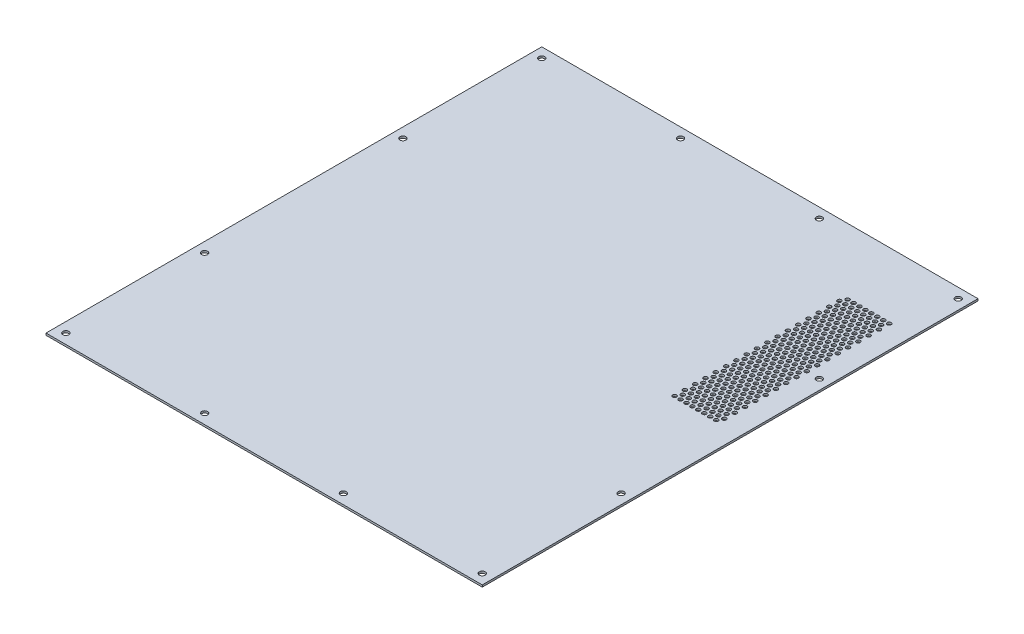
SolidWorks part; units mm, degrees
ref_plane "Front Plane" through (0, 0, 0) normal (0, 0, 1) x (1, 0, 0)
ref_plane "Top Plane" through (0, 0, 0) normal (0, 1, 0) x (1, 0, 0)
ref_plane "Right Plane" through (0, 0, 0) normal (1, 0, 0) x (0, 0, -1)
sketch "Sketch1" plane through (0, 0, 0) normal (0, 1, 0) x (1, 0, 0)
  line L0 (20, 20) -> (20, 480) construction
  line L1 (0, 0) -> (440, 0)
  line L2 (0, 0) -> (0, 500)
  line L3 (0, 500) -> (440, 500)
  line L4 (440, 0) -> (440, 500)
  line L5 (20, 480) -> (420, 480) construction
  line L6 (420, 20) -> (420, 480) construction
  line L7 (20, 20) -> (420, 20) construction
  line L9 (420, 440) -> (370, 440) construction
  line L10 (420, 440) -> (420, 260) construction
  line L11 (420, 260) -> (370, 260) construction
  line L12 (370, 440) -> (370, 260) construction
  circle A0 centre (372, 262) radius 2
  circle A1 centre (375, 267.1962) radius 2
  circle A2 centre (381, 267.1962) radius 2
  circle A3 centre (378, 262) radius 2
  circle A4 centre (387, 267.1962) radius 2
  circle A5 centre (384, 262) radius 2
  circle A6 centre (393, 267.1962) radius 2
  circle A7 centre (390, 262) radius 2
  circle A8 centre (399, 267.1962) radius 2
  circle A9 centre (396, 262) radius 2
  circle A10 centre (405, 267.1962) radius 2
  circle A11 centre (402, 262) radius 2
  circle A12 centre (411, 267.1962) radius 2
  circle A13 centre (408, 262) radius 2
  circle A14 centre (417, 267.1962) radius 2
  circle A15 centre (414, 262) radius 2
  circle A16 centre (381, 277.5862) radius 2
  circle A17 centre (378, 272.39) radius 2
  circle A18 centre (387, 277.5862) radius 2
  circle A19 centre (384, 272.39) radius 2
  circle A20 centre (393, 277.5862) radius 2
  circle A21 centre (390, 272.39) radius 2
  circle A22 centre (399, 277.5862) radius 2
  circle A23 centre (396, 272.39) radius 2
  circle A24 centre (405, 277.5862) radius 2
  circle A25 centre (402, 272.39) radius 2
  circle A26 centre (411, 277.5862) radius 2
  circle A27 centre (408, 272.39) radius 2
  circle A28 centre (417, 277.5862) radius 2
  circle A29 centre (414, 272.39) radius 2
  circle A30 centre (381, 287.9762) radius 2
  circle A31 centre (378, 282.78) radius 2
  circle A32 centre (387, 287.9762) radius 2
  circle A33 centre (384, 282.78) radius 2
  circle A34 centre (393, 287.9762) radius 2
  circle A35 centre (390, 282.78) radius 2
  circle A36 centre (399, 287.9762) radius 2
  circle A37 centre (396, 282.78) radius 2
  circle A38 centre (405, 287.9762) radius 2
  circle A39 centre (402, 282.78) radius 2
  circle A40 centre (411, 287.9762) radius 2
  circle A41 centre (408, 282.78) radius 2
  circle A42 centre (417, 287.9762) radius 2
  circle A43 centre (414, 282.78) radius 2
  circle A44 centre (381, 298.3662) radius 2
  circle A45 centre (378, 293.17) radius 2
  circle A46 centre (387, 298.3662) radius 2
  circle A47 centre (384, 293.17) radius 2
  circle A48 centre (393, 298.3662) radius 2
  circle A49 centre (390, 293.17) radius 2
  circle A50 centre (399, 298.3662) radius 2
  circle A51 centre (396, 293.17) radius 2
  circle A52 centre (405, 298.3662) radius 2
  circle A53 centre (402, 293.17) radius 2
  circle A54 centre (411, 298.3662) radius 2
  circle A55 centre (408, 293.17) radius 2
  circle A56 centre (417, 298.3662) radius 2
  circle A57 centre (414, 293.17) radius 2
  circle A58 centre (381, 308.7562) radius 2
  circle A59 centre (378, 303.56) radius 2
  circle A60 centre (387, 308.7562) radius 2
  circle A61 centre (384, 303.56) radius 2
  circle A62 centre (393, 308.7562) radius 2
  circle A63 centre (390, 303.56) radius 2
  circle A64 centre (399, 308.7562) radius 2
  circle A65 centre (396, 303.56) radius 2
  circle A66 centre (405, 308.7562) radius 2
  circle A67 centre (402, 303.56) radius 2
  circle A68 centre (411, 308.7562) radius 2
  circle A69 centre (408, 303.56) radius 2
  circle A70 centre (417, 308.7562) radius 2
  circle A71 centre (414, 303.56) radius 2
  circle A72 centre (381, 319.1462) radius 2
  circle A73 centre (378, 313.95) radius 2
  circle A74 centre (387, 319.1462) radius 2
  circle A75 centre (384, 313.95) radius 2
  circle A76 centre (393, 319.1462) radius 2
  circle A77 centre (390, 313.95) radius 2
  circle A78 centre (399, 319.1462) radius 2
  circle A79 centre (396, 313.95) radius 2
  circle A80 centre (405, 319.1462) radius 2
  circle A81 centre (402, 313.95) radius 2
  circle A82 centre (411, 319.1462) radius 2
  circle A83 centre (408, 313.95) radius 2
  circle A84 centre (417, 319.1462) radius 2
  circle A85 centre (414, 313.95) radius 2
  circle A86 centre (381, 329.5362) radius 2
  circle A87 centre (378, 324.34) radius 2
  circle A88 centre (387, 329.5362) radius 2
  circle A89 centre (384, 324.34) radius 2
  circle A90 centre (393, 329.5362) radius 2
  circle A91 centre (390, 324.34) radius 2
  circle A92 centre (399, 329.5362) radius 2
  circle A93 centre (396, 324.34) radius 2
  circle A94 centre (405, 329.5362) radius 2
  circle A95 centre (402, 324.34) radius 2
  circle A96 centre (411, 329.5362) radius 2
  circle A97 centre (408, 324.34) radius 2
  circle A98 centre (417, 329.5362) radius 2
  circle A99 centre (414, 324.34) radius 2
  circle A100 centre (381, 339.9262) radius 2
  circle A101 centre (378, 334.73) radius 2
  circle A102 centre (387, 339.9262) radius 2
  circle A103 centre (384, 334.73) radius 2
  circle A104 centre (393, 339.9262) radius 2
  circle A105 centre (390, 334.73) radius 2
  circle A106 centre (399, 339.9262) radius 2
  circle A107 centre (396, 334.73) radius 2
  circle A108 centre (405, 339.9262) radius 2
  circle A109 centre (402, 334.73) radius 2
  circle A110 centre (411, 339.9262) radius 2
  circle A111 centre (408, 334.73) radius 2
  circle A112 centre (417, 339.9262) radius 2
  circle A113 centre (414, 334.73) radius 2
  circle A114 centre (381, 350.3162) radius 2
  circle A115 centre (378, 345.12) radius 2
  circle A116 centre (387, 350.3162) radius 2
  circle A117 centre (384, 345.12) radius 2
  circle A118 centre (393, 350.3162) radius 2
  circle A119 centre (390, 345.12) radius 2
  circle A120 centre (399, 350.3162) radius 2
  circle A121 centre (396, 345.12) radius 2
  circle A122 centre (405, 350.3162) radius 2
  circle A123 centre (402, 345.12) radius 2
  circle A124 centre (411, 350.3162) radius 2
  circle A125 centre (408, 345.12) radius 2
  circle A126 centre (417, 350.3162) radius 2
  circle A127 centre (414, 345.12) radius 2
  circle A128 centre (381, 360.7062) radius 2
  circle A129 centre (378, 355.51) radius 2
  circle A130 centre (387, 360.7062) radius 2
  circle A131 centre (384, 355.51) radius 2
  circle A132 centre (393, 360.7062) radius 2
  circle A133 centre (390, 355.51) radius 2
  circle A134 centre (399, 360.7062) radius 2
  circle A135 centre (396, 355.51) radius 2
  circle A136 centre (405, 360.7062) radius 2
  circle A137 centre (402, 355.51) radius 2
  circle A138 centre (411, 360.7062) radius 2
  circle A139 centre (408, 355.51) radius 2
  circle A140 centre (417, 360.7062) radius 2
  circle A141 centre (414, 355.51) radius 2
  circle A142 centre (381, 371.0962) radius 2
  circle A143 centre (378, 365.9) radius 2
  circle A144 centre (387, 371.0962) radius 2
  circle A145 centre (384, 365.9) radius 2
  circle A146 centre (393, 371.0962) radius 2
  circle A147 centre (390, 365.9) radius 2
  circle A148 centre (399, 371.0962) radius 2
  circle A149 centre (396, 365.9) radius 2
  circle A150 centre (405, 371.0962) radius 2
  circle A151 centre (402, 365.9) radius 2
  circle A152 centre (411, 371.0962) radius 2
  circle A153 centre (408, 365.9) radius 2
  circle A154 centre (417, 371.0962) radius 2
  circle A155 centre (414, 365.9) radius 2
  circle A156 centre (381, 381.4862) radius 2
  circle A157 centre (378, 376.29) radius 2
  circle A158 centre (387, 381.4862) radius 2
  circle A159 centre (384, 376.29) radius 2
  circle A160 centre (393, 381.4862) radius 2
  circle A161 centre (390, 376.29) radius 2
  circle A162 centre (399, 381.4862) radius 2
  circle A163 centre (396, 376.29) radius 2
  circle A164 centre (405, 381.4862) radius 2
  circle A165 centre (402, 376.29) radius 2
  circle A166 centre (411, 381.4862) radius 2
  circle A167 centre (408, 376.29) radius 2
  circle A168 centre (417, 381.4862) radius 2
  circle A169 centre (414, 376.29) radius 2
  circle A170 centre (381, 391.8762) radius 2
  circle A171 centre (378, 386.68) radius 2
  circle A172 centre (387, 391.8762) radius 2
  circle A173 centre (384, 386.68) radius 2
  circle A174 centre (393, 391.8762) radius 2
  circle A175 centre (390, 386.68) radius 2
  circle A176 centre (399, 391.8762) radius 2
  circle A177 centre (396, 386.68) radius 2
  circle A178 centre (405, 391.8762) radius 2
  circle A179 centre (402, 386.68) radius 2
  circle A180 centre (411, 391.8762) radius 2
  circle A181 centre (408, 386.68) radius 2
  circle A182 centre (417, 391.8762) radius 2
  circle A183 centre (414, 386.68) radius 2
  circle A184 centre (381, 402.2662) radius 2
  circle A185 centre (378, 397.07) radius 2
  circle A186 centre (387, 402.2662) radius 2
  circle A187 centre (384, 397.07) radius 2
  circle A188 centre (393, 402.2662) radius 2
  circle A189 centre (390, 397.07) radius 2
  circle A190 centre (399, 402.2662) radius 2
  circle A191 centre (396, 397.07) radius 2
  circle A192 centre (405, 402.2662) radius 2
  circle A193 centre (402, 397.07) radius 2
  circle A194 centre (411, 402.2662) radius 2
  circle A195 centre (408, 397.07) radius 2
  circle A196 centre (417, 402.2662) radius 2
  circle A197 centre (414, 397.07) radius 2
  circle A198 centre (381, 412.6562) radius 2
  circle A199 centre (378, 407.46) radius 2
  circle A200 centre (387, 412.6562) radius 2
  circle A201 centre (384, 407.46) radius 2
  circle A202 centre (393, 412.6562) radius 2
  circle A203 centre (390, 407.46) radius 2
  circle A204 centre (399, 412.6562) radius 2
  circle A205 centre (396, 407.46) radius 2
  circle A206 centre (405, 412.6562) radius 2
  circle A207 centre (402, 407.46) radius 2
  circle A208 centre (411, 412.6562) radius 2
  circle A209 centre (408, 407.46) radius 2
  circle A210 centre (417, 412.6562) radius 2
  circle A211 centre (414, 407.46) radius 2
  circle A212 centre (381, 423.0462) radius 2
  circle A213 centre (378, 417.85) radius 2
  circle A214 centre (387, 423.0462) radius 2
  circle A215 centre (384, 417.85) radius 2
  circle A216 centre (393, 423.0462) radius 2
  circle A217 centre (390, 417.85) radius 2
  circle A218 centre (399, 423.0462) radius 2
  circle A219 centre (396, 417.85) radius 2
  circle A220 centre (405, 423.0462) radius 2
  circle A221 centre (402, 417.85) radius 2
  circle A222 centre (411, 423.0462) radius 2
  circle A223 centre (408, 417.85) radius 2
  circle A224 centre (417, 423.0462) radius 2
  circle A225 centre (414, 417.85) radius 2
  circle A226 centre (381, 433.4362) radius 2
  circle A227 centre (378, 428.24) radius 2
  circle A228 centre (387, 433.4362) radius 2
  circle A229 centre (384, 428.24) radius 2
  circle A230 centre (393, 433.4362) radius 2
  circle A231 centre (390, 428.24) radius 2
  circle A232 centre (399, 433.4362) radius 2
  circle A233 centre (396, 428.24) radius 2
  circle A234 centre (405, 433.4362) radius 2
  circle A235 centre (402, 428.24) radius 2
  circle A236 centre (411, 433.4362) radius 2
  circle A237 centre (408, 428.24) radius 2
  circle A238 centre (417, 433.4362) radius 2
  circle A239 centre (414, 428.24) radius 2
  circle A240 centre (375, 277.5862) radius 2
  circle A241 centre (372, 272.39) radius 2
  circle A242 centre (375, 287.9762) radius 2
  circle A243 centre (372, 282.78) radius 2
  circle A244 centre (375, 298.3662) radius 2
  circle A245 centre (372, 293.17) radius 2
  circle A246 centre (375, 308.7562) radius 2
  circle A247 centre (372, 303.56) radius 2
  circle A248 centre (375, 319.1462) radius 2
  circle A249 centre (372, 313.95) radius 2
  circle A250 centre (375, 329.5362) radius 2
  circle A251 centre (372, 324.34) radius 2
  circle A252 centre (375, 339.9262) radius 2
  circle A253 centre (372, 334.73) radius 2
  circle A254 centre (375, 350.3162) radius 2
  circle A255 centre (372, 345.12) radius 2
  circle A256 centre (375, 360.7062) radius 2
  circle A257 centre (372, 355.51) radius 2
  circle A258 centre (375, 371.0962) radius 2
  circle A259 centre (372, 365.9) radius 2
  circle A260 centre (375, 381.4862) radius 2
  circle A261 centre (372, 376.29) radius 2
  circle A262 centre (375, 391.8762) radius 2
  circle A263 centre (372, 386.68) radius 2
  circle A264 centre (375, 402.2662) radius 2
  circle A265 centre (372, 397.07) radius 2
  circle A266 centre (375, 412.6562) radius 2
  circle A267 centre (372, 407.46) radius 2
  circle A268 centre (375, 423.0462) radius 2
  circle A269 centre (372, 417.85) radius 2
  circle A270 centre (375, 433.4362) radius 2
  circle A271 centre (372, 428.24) radius 2
  circle A272 centre (10, 490) radius 3
  circle A273 centre (430, 490) radius 3
  circle A274 centre (430, 10) radius 3
  circle A275 centre (10, 10) radius 3
  circle A276 centre (430, 150) radius 3
  circle A277 centre (430, 350) radius 3
  circle A278 centre (10, 150) radius 3
  circle A279 centre (10, 350) radius 3
  circle A280 centre (150, 10) radius 3
  circle A281 centre (290, 10) radius 3
  circle A282 centre (150, 490) radius 3
  circle A283 centre (290, 490) radius 3
  point P566 (430, 163.1757)
  point P569 (430, 339.9262)
  point P572 (10, 146.949)
  point P575 (10, 345.12)
  point P578 (142.561, 10)
  point P581 (284.7457, 10)
  point P582 (0, 0)
  point P585 (150, 490)
  point P588 (290, 490)
  dimension "D7" = 2
  dimension "D8" = 2
  dimension "D12" = 10
  dimension "D14" = 10
  dimension "D21" = 6
  dimension "D22" = 4
  dimension "D2" = 180
  dimension "D3" = 50
  dimension "D4" = 60
  dimension "D5" = 500
  dimension "D6" = 440
  dimension "D9" = 8
  dimension "D10" = 17
  dimension "D11" = 6
  dimension "D13" = 5.1962
  dimension "D15" = 10
  dimension "D16" = 10
  dimension "D17" = 10
  dimension "D18" = 10
  dimension "D19" = 10
  dimension "D20" = 10
  dimension "D23" = 150
  dimension "D24" = 350
  dimension "D25" = 150
  dimension "D26" = 150
  dimension "D27" = 350
  dimension "D28" = 150
  dimension "D29" = 150
  dimension "D30" = 150
  dimension "D31" = 150
  dimension "D32" = 150
  dimension "D1" = 20
extrude "Boss-Extrude1" add sketch "Sketch1" along normal blind 2
